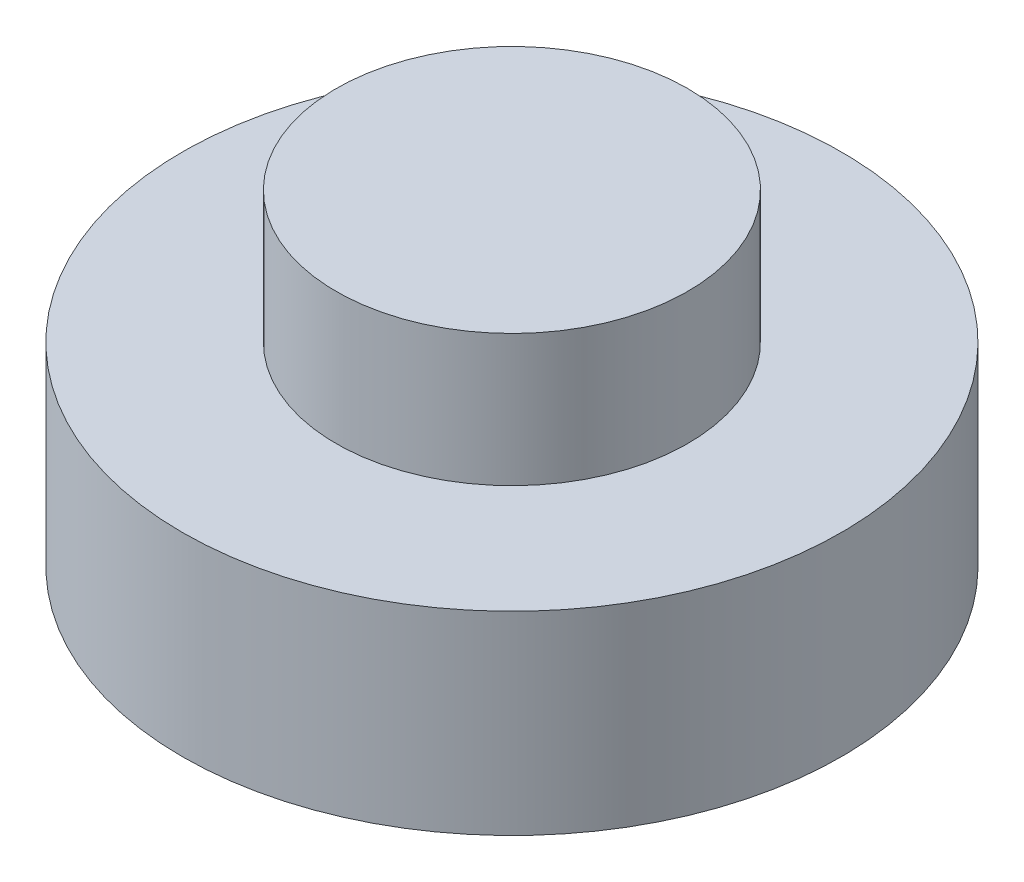
SolidWorks part; units mm, degrees
ref_plane "Front Plane" through (0, 0, 0) normal (0, 0, 1) x (1, 0, 0)
ref_plane "Top Plane" through (0, 0, 0) normal (0, 1, 0) x (1, 0, 0)
ref_plane "Right Plane" through (0, 0, 0) normal (1, 0, 0) x (0, 0, -1)
sketch "Sketch1" plane through (0, 0, 0) normal (0, 1, 0) x (1, 0, 0)
  circle A0 centre (0, 0) radius 4
  circle A1 centre (0, 0) radius 7.5
  dimension "D1" = 8
  dimension "D2" = 15
extrude "Boss-Extrude1" add sketch "Sketch1" along normal blind 4.42
extrude "Boss-Extrude2" add sketch "Sketch1<2>" along normal blind 7.42 contours A0 region at (0, 0, 0)
sketch "Sketch1<2>" plane through (0, 0, 0) normal (0, 1, 0) x (1, 0, 0) same geometry as "Sketch1"
